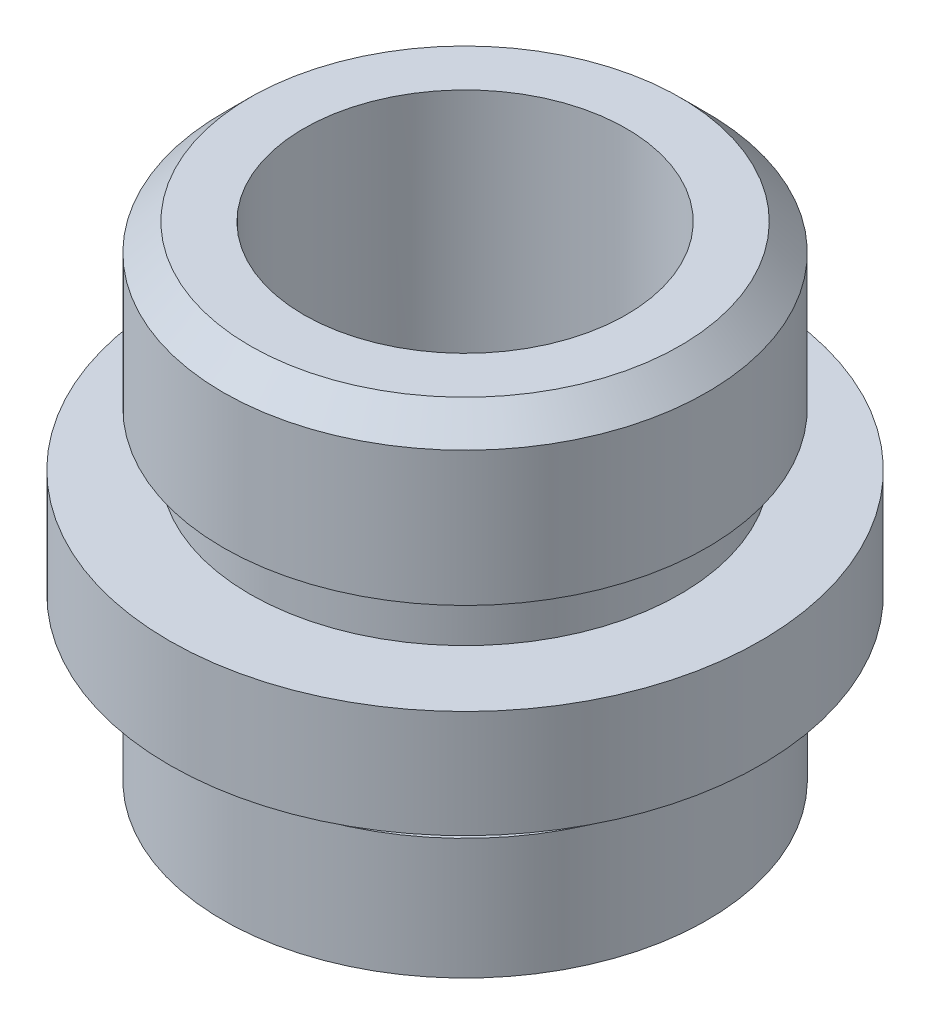
SolidWorks part; units mm, degrees
ref_plane "Front Plane" through (0, 0, 0) normal (0, 0, 1) x (1, 0, 0)
ref_plane "Top Plane" through (0, 0, 0) normal (0, 1, 0) x (1, 0, 0)
ref_plane "Right Plane" through (0, 0, 0) normal (1, 0, 0) x (0, 0, -1)
sketch "Sketch1" plane through (0, 0, 0) normal (0, 1, 0) x (1, 0, 0)
  circle A0 centre (0, 0) radius 22
extrude "Boss-Extrude1" add sketch "Sketch1" along normal blind 4 and the other way blind 4
sketch "Sketch2" plane through (0, 4, 0) normal (0, 1, 0) x (1, 0, 0)
  circle A0 centre (0, 0) radius 16
extrude "Boss-Extrude2" add sketch "Sketch2" along normal blind 4
sketch "Sketch3" plane through (0, 8, 0) normal (0, 1, 0) x (1, 0, 0)
  circle A0 centre (0, 0) radius 18
extrude "Boss-Extrude3" add sketch "Sketch3" along normal blind 12
sketch "Sketch4" plane through (0, -4, 0) normal (0, -1, 0) x (1, 0, 0)
  circle A0 centre (0, 0) radius 16
extrude "Boss-Extrude4" add sketch "Sketch4" along normal blind 3
sketch "Sketch5" plane through (0, -7, 0) normal (0, -1, 0) x (1, 0, 0)
  circle A0 centre (0, 0) radius 18
extrude "Boss-Extrude5" add sketch "Sketch5" along normal blind 9
chamfer "Chamfer1" distance 2 angle 45 1 edges at (0, 20, 18)
sketch "Sketch6" plane through (0, 20, 0) normal (0, 1, 0) x (1, 0, 0)
  circle A0 centre (0, 0) radius 12
extrude "Cut-Extrude1" cut sketch "Sketch6" against normal up to surface (36 mm away) contours A0 up to face at (0, -16, -18)
